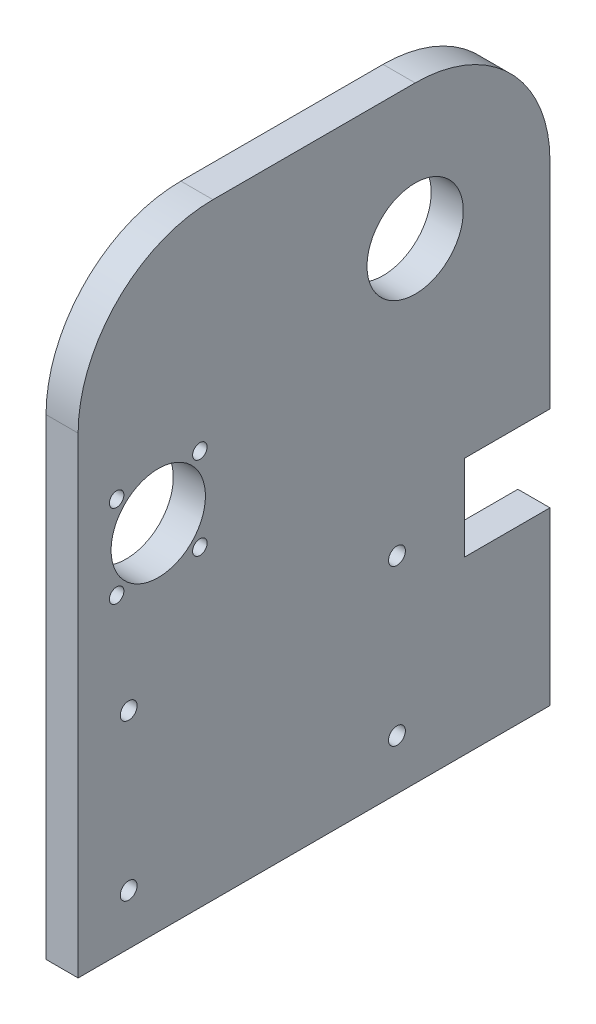
SolidWorks part; units mm, degrees
ref_plane "Front Plane" through (0, 0, 0) normal (0, 0, 1) x (1, 0, 0)
ref_plane "Top Plane" through (0, 0, 0) normal (0, 1, 0) x (1, 0, 0)
ref_plane "Right Plane" through (0, 0, 0) normal (1, 0, 0) x (0, 0, -1)
sketch "Sketch1" plane through (0, 0, 0) normal (0, 1, 0) x (1, 0, 0)
  line L1 (-4.7625, 70) -> (4.7625, 70)
  line L2 (-4.7625, 70) -> (-4.7625, -70)
  line L3 (-4.7625, -70) -> (4.7625, -70)
  line L4 (4.7625, 70) -> (4.7625, -70)
  line L5 (-4.7625, 70) -> (4.7625, -70) construction
  line L6 (-4.7625, -70) -> (4.7625, 70) construction
  point P0 (0, 0)
  dimension "D1" = 140
  dimension "D2" = 9.525
extrude "Boss-Extrude1" add sketch "Sketch1" along normal mid plane 180
sketch "Sketch5" plane through (-4.7625, 0, 0) normal (-1, 0, 0) x (0, 0, 1)
  line L1 (-70, 90) -> (-70, -90) construction
  line L2 (-70, -13.7746) -> (-44.6, -13.7746)
  line L3 (-70, -13.7746) -> (-70, -39.1746)
  line L4 (-70, -39.1746) -> (-44.6, -39.1746)
  line L5 (-70, -90) -> (70, -90) construction
  line L6 (-44.6, -13.7746) -> (-44.6, -39.1746)
  dimension "D3" = 25.4
  dimension "D1" = 50.8254
  dimension "D2" = 25.4
sketch "Sketch3" plane through (-4.7625, 0, 0) normal (-1, 0, 0) x (0, 0, 1)
  line L0 (46.229, 15) -> (56.2489, 25.02) construction
  line L2 (-70, 90) -> (-70, -90) construction
  line L3 (-45.4613, 15) -> (44.137, 15) construction
  line L6 (46.229, 26.0113) -> (46.229, -23.3547) construction
  line L7 (-70, 90) -> (70, 90) construction
  circle A0 centre (-30, 50) radius 14.29
  circle A1 centre (33.8811, 27.3479) radius 2.15
  circle A2 centre (58.5768, 27.3479) radius 2.15
  circle A3 centre (33.8811, 2.6521) radius 2.15
  circle A4 centre (58.5768, 2.6521) radius 2.15
  circle A5 centre (46.229, 15) radius 14
  circle A6 centre (46.229, 15) radius 17.4625 construction
  dimension "D1" = 28.58
  dimension "D2" = 40
  dimension "D3" = 45
  dimension "D4" = 12.3479
  dimension "D7" = 28
  dimension "D8" = 4.3
  dimension "D10" = 35
  dimension "Bolt circle" = 34.925
  dimension "D5" = 83.88
  dimension "D9" = 40
extrude "Cut-Extrude2" cut sketch "Sketch3" against normal blind 28.575
extrude "Cut-Extrude4" cut sketch "Sketch5" against normal through all
ref_axis "Axis1" through (4.7625, 50, -30) along (-1, 0, 0)
hole_wizard "M6 Tapped Hole1" positions "Sketch7" profile "Sketch6" tap size "M6" standard "DIN"
sketch "Sketch7" plane through (0, 0, -44.6) normal (0, 0, -1) x (-1, 0, 0)
  line L1 (-4.7625, -39.1746) -> (4.7625, -39.1746) construction
  point P0 (0, -26.4746)
  dimension "D1" = 12.7
sketch "Sketch6" plane through (0, -26.4746, -44.6) normal (1, 0, 0) x (0, 1, 0)
  line L0 (0, 0) -> (0, 11.5022)
  line L1 (0, 11.5022) -> (2.5, 10)
  line L2 (2.5, 10) -> (2.5, 0)
  line L5 (2.5, 0) -> (0, 0)
  line L10 (0, 11.5022) -> (-2.5, 10) construction
  line L11 (0, -6.35) -> (0, 107.95) construction
  dimension "Tap Drill Dia." = 5
  dimension "Tap Drill Depth" = 10
  dimension "Drill Angle" = 118
cosmetic thread "Hole Thread1" parameters "D1"=10, "D2"=6
hole_wizard "M6 Tapped Hole2" positions "Sketch9" profile "Sketch8" tap size "M6" standard "DIN" end condition through all
sketch "Sketch9" plane through (-4.7625, 0, 0) normal (-1, 0, 0) x (0, 0, 1)
  line L0 (-44.6, -39.1746) -> (-44.6, -13.7746) construction
  line L1 (-70, -39.1746) -> (-70, -90) construction
  line L2 (70, 90) -> (70, -90) construction
  line L3 (-44.6, -13.7746) -> (-70, -13.7746) construction
  line L5 (-70, -90) -> (70, -90) construction
  point P0 (-24.6, -28.7746)
  point P2 (55, -28.7746)
  point P4 (-24.6, -75)
  point P6 (55, -75)
  dimension "D1" = 20
  dimension "D2" = 45.4
  dimension "D3" = 15
  dimension "D4" = 15
  dimension "D5" = 15
  dimension "D6" = 15
  dimension "D7" = 15
  dimension "D8" = 15
sketch "Sketch8" plane through (-4.7625, -28.7746, -24.6) normal (0, 1, 0) x (0, 0, 1)
  line L0 (0, 0) -> (0, 9.525)
  line L1 (0, 9.525) -> (2.5, 9.525)
  line L2 (2.5, 9.525) -> (2.5, 0)
  line L5 (2.5, 0) -> (0, 0)
  line L11 (0, -6.35) -> (0, 107.95) construction
  dimension "Thru Tap Drill Dia." = 5
  dimension "Thru Tap Drill Depth" = 9.525
cosmetic thread "Hole Thread2" parameters "D2"=6
cosmetic thread "Hole Thread3" parameters "D2"=6
cosmetic thread "Hole Thread4" parameters "D2"=6
cosmetic thread "Hole Thread5" parameters "D2"=6
fillet "Fillet1" radius 40 2 edges at (0, 90, 70) (0, 90, -70)
